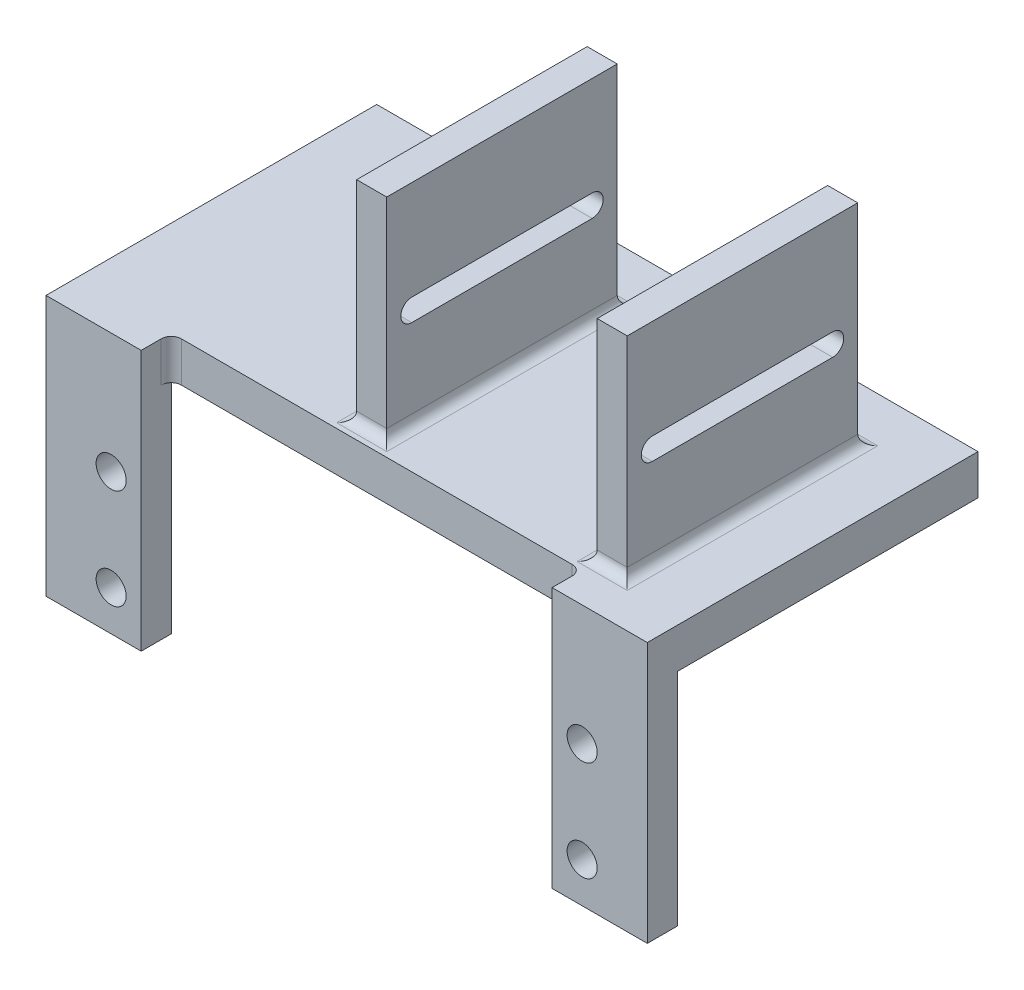
SolidWorks part; units mm, degrees
ref_plane "Front Plane" through (0, 0, 0) normal (0, 0, 1) x (1, 0, 0)
ref_plane "Top Plane" through (0, 0, 0) normal (0, 1, 0) x (1, 0, 0)
ref_plane "Right Plane" through (0, 0, 0) normal (1, 0, 0) x (0, 0, -1)
sketch "Sketch1" plane through (0, 0, 0) normal (0, 1, 0) x (1, 0, 0)
  line L1 (-30, -15) -> (30, -15)
  line L2 (-30, -15) -> (-30, 15)
  line L3 (-30, 15) -> (30, 15)
  line L4 (30, -15) -> (30, 15)
  line L5 (-30, -15) -> (30, 15) construction
  line L6 (-30, 15) -> (30, -15) construction
  point P0 (0, 0)
  dimension "D1" = 60
  dimension "D2" = 30
extrude "Boss-Extrude1" add sketch "Sketch1" along normal blind 4
sketch "Sketch2" plane through (0, 4, 0) normal (0, 1, 0) x (1, 0, 0)
  line L0 (0, -55) -> (0, 55) construction
  line L1 (-30, -15) -> (-20.5, -15)
  line L2 (-30, -15) -> (-30, -18)
  line L3 (-30, -18) -> (-20.5, -18)
  line L4 (-20.5, -15) -> (-20.5, -18)
  line L5 (30, -18) -> (20.5, -18)
  line L6 (20.5, -15) -> (20.5, -18)
  line L7 (30, -15) -> (20.5, -15)
  line L8 (30, -15) -> (30, -18)
  line L9 (-30, -15) -> (30, -15) construction
  line L10 (-30, 15) -> (-30, -15) construction
  dimension "D1" = 3
  dimension "D3" = 41
extrude "Boss-Extrude2" add sketch "Sketch2" against normal blind 26
sketch "Sketch3" plane through (0, 0, 18) normal (0, 0, 1) x (1, 0, 0)
  line L0 (0, -55) -> (0, 55) construction
  line L1 (-20.5, 0) -> (20.5, 0) construction
  circle A0 centre (-23.5, -8) radius 1.5
  circle A1 centre (-23.5, -18) radius 1.5
  circle A2 centre (23.5, -18) radius 1.5
  circle A3 centre (23.5, -8) radius 1.5
  dimension "D1" = 3
  dimension "D2" = 3
  dimension "D3" = 47
  dimension "D4" = 10
  dimension "D5" = 8
extrude "Cut-Extrude1" cut sketch "Sketch3" against normal blind 4
ref_plane "Plane1" through (10, 0, 0) normal (1, 0, 0) x (0, 0, -1)
sketch "Sketch4" plane through (0, 4, 0) normal (0, 1, 0) x (1, 0, 0)
  line L0 (10, -17.7593) -> (10, 17.7593) construction
  line L1 (-3.5, -13.5) -> (-0.5, -13.5)
  line L2 (-3.5, -13.5) -> (-3.5, 9.5)
  line L3 (-3.5, 9.5) -> (-0.5, 9.5)
  line L4 (-0.5, -13.5) -> (-0.5, 9.5)
  line L5 (-3.5, -13.5) -> (-0.5, 9.5) construction
  line L6 (-3.5, 9.5) -> (-0.5, -13.5) construction
  line L7 (23.5, 9.5) -> (20.5, 9.5)
  line L8 (20.5, -13.5) -> (20.5, 9.5)
  line L9 (23.5, -13.5) -> (20.5, -13.5)
  line L10 (23.5, -13.5) -> (23.5, 9.5)
  line L11 (23.5, 9.5) -> (20.5, -13.5) construction
  line L12 (23.5, -13.5) -> (20.5, 9.5) construction
  line L13 (-20.5, -15) -> (20.5, -15) construction
  point P0 (-2, -2)
  point P11 (22, -2)
  dimension "D1" = 21
  dimension "D2" = 23
  dimension "D3" = 13
  dimension "D4" = 3
extrude "Boss-Extrude4" add sketch "Sketch4" along normal blind 21
sketch "Sketch5" plane through (-3.5, 0, 0) normal (-1, 0, 0) x (0, 0, 1)
  line L0 (-7, 14) -> (11, 14) construction
  line L4 (-7, 15.1) -> (11, 15.1)
  line L7 (-7, 12.9) -> (11, 12.9)
  line L8 (-9.5, 4) -> (13.5, 4) construction
  line L9 (13.5, 25) -> (13.5, 4) construction
  arc A2 (-7, 15.1) -> (-7, 12.9) centre (-7, 14) ccw
  arc A3 (11, 12.9) -> (11, 15.1) centre (11, 14) ccw
  point P2 (2, 14)
  dimension "D1" = 10
  dimension "D2" = 1.1
  dimension "D3" = 18
  dimension "D4" = 2.5
extrude "Cut-Extrude2" cut sketch "Sketch5" against normal blind 27
fillet "Fillet1" radius 1 10 edges at (20.5, 2, 15) (-20.5, 2, 15) (-2, 4, -9.5) (22, 4, -9.5) (23.5, 4, 2) (22, 4, 13.5) (20.5, 4, 2) (-2, 4, 13.5) (-0.5, 4, 2) (-3.5, 4, 2)
